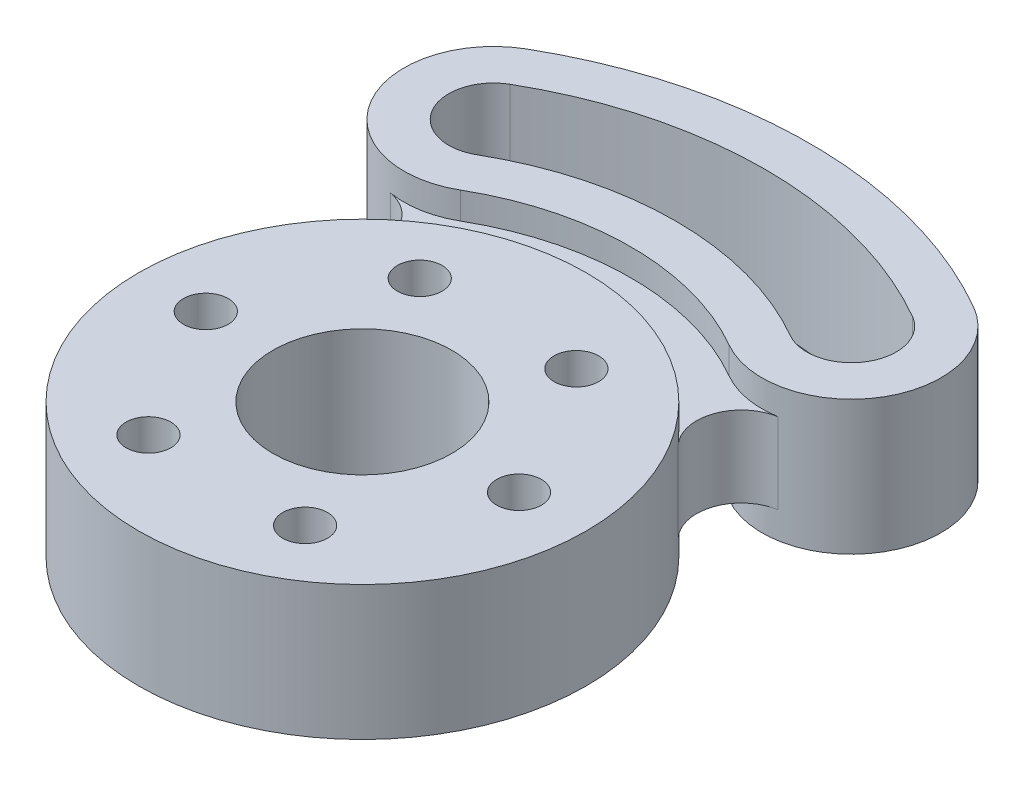
SolidWorks part; units mm, degrees
ref_plane "Front Plane" through (0, 0, 0) normal (0, 0, 1) x (1, 0, 0)
ref_plane "Top Plane" through (0, 0, 0) normal (0, 1, 0) x (1, 0, 0)
ref_plane "Right Plane" through (0, 0, 0) normal (1, 0, 0) x (0, 0, -1)
sketch "Sketch1" plane through (0, 0, 0) normal (0, 1, 0) x (1, 0, 0)
  arc A0 (-40, 69.282) -> (40, 69.282) centre (0, 0) cw construction
  arc A1 (45, 77.9423) -> (-45, 77.9423) centre (0, 0) ccw
  arc A2 (35, 60.6218) -> (-35, 60.6218) centre (0, 0) ccw
  arc A3 (35, 60.6218) -> (45, 77.9423) centre (40, 69.282) ccw
  arc A4 (-45, 77.9423) -> (-35, 60.6218) centre (-40, 69.282) ccw
  circle A5 centre (0, 0) radius 20
  circle A6 centre (0, 0) radius 50
  circle A7 centre (0, 0) radius 35 construction
  circle A8 centre (35, 0) radius 5
  arc A9 (50, 86.6025) -> (-50, 86.6025) centre (0, 0) ccw
  arc A10 (-50, 86.6025) -> (-30, 51.9615) centre (-40, 69.282) ccw
  arc A11 (30, 51.9615) -> (-30, 51.9615) centre (0, 0) ccw
  arc A12 (30, 51.9615) -> (50, 86.6025) centre (40, 69.282) ccw
  arc A13 (43.3255, 49.5604) -> (37.4902, 33.083) centre (44.9882, 39.6996) ccw
  arc A14 (-37.4902, 33.083) -> (-43.3255, 49.5604) centre (-44.9882, 39.6996) ccw
  circle A15 centre (17.5, -30.3109) radius 5
  circle A16 centre (-17.5, -30.3109) radius 5
  circle A17 centre (-35, 0) radius 5
  circle A18 centre (-17.5, 30.3109) radius 5
  circle A19 centre (17.5, 30.3109) radius 5
  point P3 (0, 80)
  point P11 (0, 0)
  point P18 (0, 70)
  point P26 (0, 0)
  point P31 (0, 0)
  dimension "D1" = 40
  dimension "D2" = 100
  dimension "D3" = 10
  dimension "70" = 70
  dimension "D4" = 20
  dimension "D5" = 10
  dimension "D6" = 20
  dimension "D8" = 80
  dimension "D7" = 30
  dimension "D9" = 6
extrude "Boss-Extrude1" add sketch "Sketch1" along normal mid plane 30 contours A11 A12 A9 A10 A4 A1 A3 A2 | A6 A19 A18 A17 A16 A15 A8 A5 region at (-17.1844, 0, 45.4453) region at (36.6844, 0, -50.8811)
extrude "Boss-Extrude2" add sketch "Sketch1<3>" along normal mid plane 18 contours A14 A6 A13 A12 A11 A10 region at (0, 0, -50.4511)
sketch "Sketch1<3>" plane through (0, 0, 0) normal (0, 1, 0) x (1, 0, 0) same geometry as "Sketch1"
